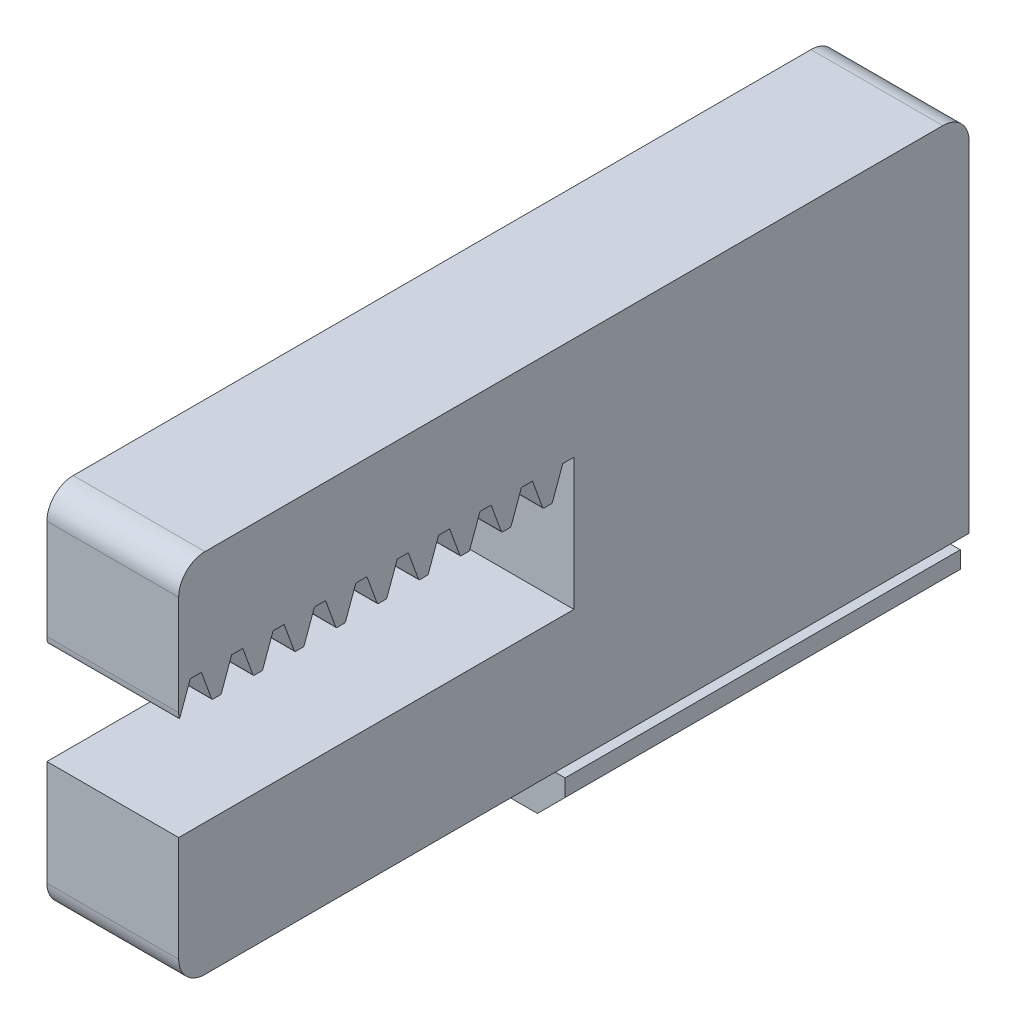
SolidWorks part; units mm, degrees
ref_plane "Front Plane" through (0, 0, 0) normal (0, 0, 1) x (1, 0, 0)
ref_plane "Top Plane" through (0, 0, 0) normal (0, 1, 0) x (1, 0, 0)
ref_plane "Right Plane" through (0, 0, 0) normal (1, 0, 0) x (0, 0, -1)
sketch "Sketch1" plane through (0, 0, 0) normal (1, 0, 0) x (0, 0, -1)
  line L0 (38.1, 0) -> (38.1, -6.096)
  line L1 (0, 35.306) -> (38.1, 35.306)
  line L2 (0, 35.306) -> (0, 22.606)
  line L3 (0, 22.606) -> (38.1, 22.606)
  line L5 (38.1, 35.306) -> (76.2, 35.306)
  line L6 (38.1, 22.606) -> (38.1, 12.7)
  line L7 (38.1, -6.096) -> (76.2, -6.096)
  line L8 (76.2, 35.306) -> (76.2, -6.096)
  line L9 (38.1, 12.7) -> (0, 12.7)
  line L11 (38.1, 0) -> (0, 0)
  line L12 (0, 12.7) -> (0, 0)
  dimension "D1" = 12.7
  dimension "D2" = 12.7
  dimension "D3" = 9.906
  dimension "D4" = 38.1
  dimension "D5" = 38.1
  dimension "D6" = 6.096
extrude "Boss-Extrude1" add sketch "Sketch1" along normal mid plane 12.7
sketch "Sketch2" plane through (6.35, 0, 0) normal (1, 0, 0) x (0, 0, -1)
  line L0 (29.0499, 25.404) -> (30.1203, 25.404) construction
  line L1 (31.0948, 22.7267) -> (30.1203, 25.404) construction
  line L2 (31.8261, 22.5592) -> (31.334, 22.5592) construction
  line L3 (33.0397, 25.404) -> (32.0653, 22.7267) construction
  line L4 (33.0397, 25.404) -> (34.1102, 25.404) construction
  line L5 (35.0846, 22.7267) -> (34.1102, 25.404) construction
  line L6 (35.8159, 22.5592) -> (35.3238, 22.5592) construction
  line L7 (37.0296, 25.404) -> (36.0551, 22.7267) construction
  line L8 (37.0296, 25.404) -> (38.1, 25.404) construction
  line L9 (29.0499, 25.404) -> (30.1203, 25.404)
  line L10 (31.0948, 22.7267) -> (30.1203, 25.404)
  line L11 (31.8261, 22.5592) -> (31.334, 22.5592)
  line L12 (33.0397, 25.404) -> (32.0653, 22.7267)
  line L13 (33.0397, 25.404) -> (34.1102, 25.404)
  line L14 (35.0846, 22.7267) -> (34.1102, 25.404)
  line L15 (35.8159, 22.5592) -> (35.3238, 22.5592)
  line L16 (37.0296, 25.404) -> (36.0551, 22.7267)
  line L17 (37.0296, 25.404) -> (38.1, 25.404)
  line L18 (38.1, 25.404) -> (38.1, 12.7)
  line L19 (38.1, 22.606) -> (38.1, 12.7) construction
  line L20 (38.1, 12.7) -> (29.0499, 12.7)
  line L21 (29.0499, 12.7) -> (29.0499, 25.404)
  line L22 (38.1, 12.7) -> (0, 12.7) construction
  arc A0 (31.0948, 22.7267) -> (31.334, 22.5592) centre (31.334, 22.8138) ccw construction
  arc A1 (31.8261, 22.5592) -> (32.0653, 22.7267) centre (31.8261, 22.8138) ccw construction
  arc A2 (35.0846, 22.7267) -> (35.3238, 22.5592) centre (35.3238, 22.8138) ccw construction
  arc A3 (35.8159, 22.5592) -> (36.0551, 22.7267) centre (35.8159, 22.8138) ccw construction
  arc A4 (31.0948, 22.7267) -> (31.334, 22.5592) centre (31.334, 22.8138) ccw
  arc A5 (31.8261, 22.5592) -> (32.0653, 22.7267) centre (31.8261, 22.8138) ccw
  arc A6 (35.0846, 22.7267) -> (35.3238, 22.5592) centre (35.3238, 22.8138) ccw
  arc A7 (35.8159, 22.5592) -> (36.0551, 22.7267) centre (35.8159, 22.8138) ccw
extrude "Cut-Extrude1" cut sketch "Sketch2" against normal through all
pattern_linear "LPattern1" count 10 spacing 3.9898 along (0, 0, 1) of "Cut-Extrude1"
sketch "Sketch3" plane through (0, 0, -76.2) normal (0, 0, -1) x (-1, 0, 0)
  line L1 (2.8393, -6.096) -> (5.5, -3.4353) construction
  line L2 (5.5, -3.4353) -> (5.5, -1.796) construction
  line L3 (5.5, -1.796) -> (3.125, -1.796) construction
  line L4 (3.125, -1.796) -> (3.125, -1.451) construction
  line L5 (3.125, -1.451) -> (4.58, 0.004) construction
  line L6 (15.42, 0.004) -> (4.58, 0.004) construction
  line L7 (-4.58, 0.004) -> (-9.5, 0.004) construction
  line L8 (-3.125, -1.451) -> (-4.58, 0.004) construction
  line L9 (-3.125, -1.796) -> (-3.125, -1.451) construction
  line L10 (-5.5, -1.796) -> (-3.125, -1.796) construction
  line L11 (-5.5, -3.4353) -> (-5.5, -1.796) construction
  line L12 (-2.8393, -6.096) -> (-5.5, -3.4353) construction
  line L15 (2.8393, -6.096) -> (5.5, -3.4353)
  line L16 (5.5, -3.4353) -> (5.5, -1.796)
  line L17 (5.5, -1.796) -> (3.125, -1.796)
  line L18 (3.125, -1.796) -> (3.125, -1.451)
  line L19 (3.125, -1.451) -> (4.58, 0.004)
  line L20 (15.42, 0.004) -> (4.58, 0.004)
  line L21 (-4.58, 0.004) -> (-9.5, 0.004)
  line L22 (-3.125, -1.451) -> (-4.58, 0.004)
  line L23 (-3.125, -1.796) -> (-3.125, -1.451)
  line L24 (-5.5, -1.796) -> (-3.125, -1.796)
  line L25 (-5.5, -3.4353) -> (-5.5, -1.796)
  line L26 (-2.8393, -6.096) -> (-5.5, -3.4353)
  line L29 (-9.5, 0.004) -> (-6.35, -6.096)
  line L30 (-6.35, -6.096) -> (-2.8393, -6.096)
  line L31 (2.8393, -6.096) -> (6.35, -6.096)
  line L32 (6.35, -6.096) -> (15.42, 0.004)
extrude "Cut-Extrude2" cut sketch "Sketch3" against normal through all
fillet "Fillet1" radius 2.54 4 edges at (0, 22.606, 0) (0, 0, 0) (0, 35.306, 0) (0, 35.306, -76.2)
